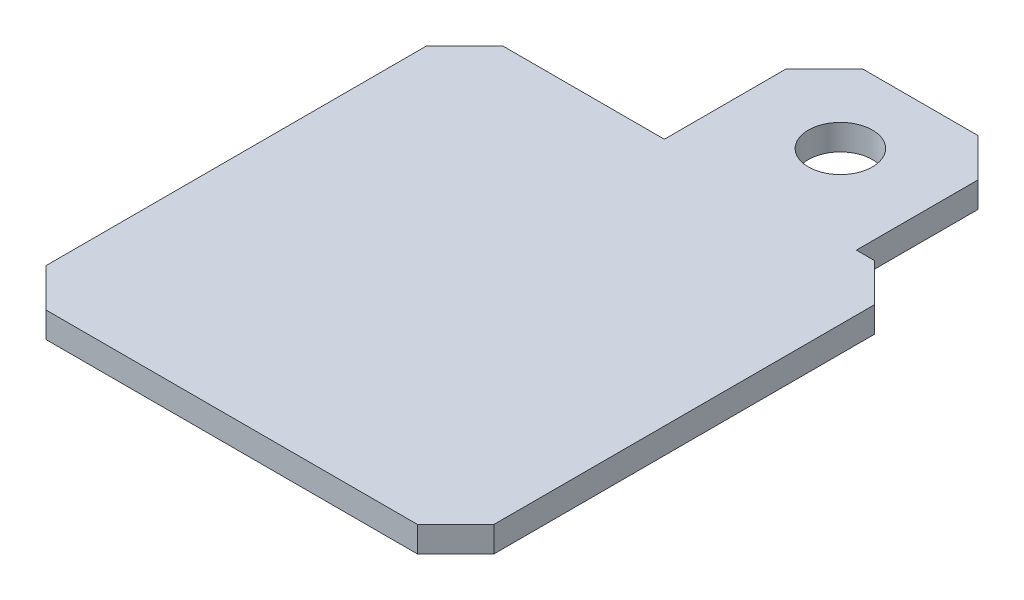
SolidWorks part; units mm, degrees
ref_plane "Front Plane" through (0, 0, 0) normal (0, 0, 1) x (1, 0, 0)
ref_plane "Top Plane" through (0, 0, 0) normal (0, 1, 0) x (1, 0, 0)
ref_plane "Right Plane" through (0, 0, 0) normal (1, 0, 0) x (0, 0, -1)
sketch "Sketch1" plane through (0, 0, 0) normal (0, 1, 0) x (1, 0, 0)
  line L0 (0, 17.5) -> (0, 30) construction
  line L1 (-17.5, -17.5) -> (17.5, -17.5)
  line L2 (-17.5, -17.5) -> (-17.5, 17.5)
  line L3 (-17.5, 17.5) -> (17.5, 17.5)
  line L4 (17.5, -17.5) -> (17.5, 17.5)
  line L5 (-17.5, -17.5) -> (17.5, 17.5) construction
  line L6 (-17.5, 17.5) -> (17.5, -17.5) construction
  line L7 (7.5, 17.5) -> (-7.5, 17.5) construction
  line L8 (-7.5, 17.5) -> (-7.5, 30) construction
  line L9 (7.5, 17.5) -> (7.5, 30)
  line L10 (7.5, 30) -> (-1.9, 30)
  line L11 (7.5, 17.5) -> (13.1, 17.5) construction
  line L12 (13.1, 17.5) -> (13.1, 30)
  line L13 (13.1, 30) -> (7.5, 30)
  line L14 (-7.5, 17.5) -> (-1.9, 17.5) construction
  line L15 (-1.9, 17.5) -> (-1.9, 30)
  line L16 (13.1, 23.75) -> (-1.9, 23.75) construction
  line L17 (-17.5, -17.5) -> (-17.5, -18.2)
  line L18 (-17.5, -18.2) -> (17.5, -18.2)
  line L19 (17.5, -18.2) -> (17.5, -17.5)
  circle A1 centre (0, 23.75) radius 2.5 construction
  circle A2 centre (5.6, 23.75) radius 2.5
  point P0 (0, 0)
  point P11 (0, 17.5)
  dimension "D3" = 5
  dimension "D7" = 5
  dimension "D1" = 35
  dimension "D2" = 12.5
  dimension "D4" = 7.5
  dimension "D5" = 5.6
  dimension "D6" = 5.6
  dimension "D8" = 0.7
extrude "Boss-Extrude1" add sketch "Sketch1" along normal blind 2 contours A2 L9 L3 L12 L13 | A2 L9 L10 L15 L3 | L18 L19 L1 L17 | L1 L4 L3 L2 region at (0, 0, 0) region at (0, 0, 17.85) region at (2.3123, 0, -23.75) region at (10.3497, 0, -23.75)
chamfer "Chamfer1" distance 3 angle 45 6 edges at (13.1, 1, -30) (-1.9, 1, -30) (17.5, 1, 18.2) (17.5, 1, -17.5) (-17.5, 1, 18.2) (-17.5, 1, -17.5)
